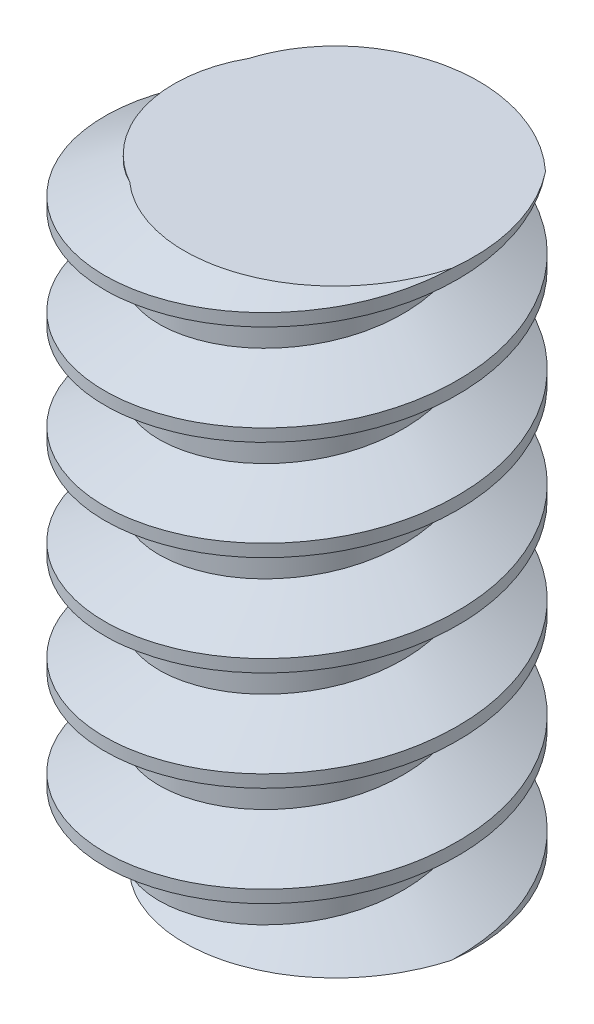
SolidWorks part; units mm, degrees
ref_plane "Front Plane" through (0, 0, 0) normal (0, 0, 1) x (1, 0, 0)
ref_plane "Top Plane" through (0, 0, 0) normal (0, 1, 0) x (1, 0, 0)
ref_plane "Right Plane" through (0, 0, 0) normal (1, 0, 0) x (0, 0, -1)
sketch "Sketch1" plane through (0, 0, 0) normal (0, 1, 0) x (1, 0, 0)
  circle A0 centre (0, 0) radius 4.5
  dimension "D1" = 9
extrude "Boss-Extrude1" add sketch "Sketch1" along normal blind 15.24
thread "Thread1" pitch 2.54 method cut profile "Thread Profile2" start angle 0, offset 3.54, length 0, pitch 2.54, diameter 9
ref_plane "Plane2" through (-4.5, 18.78, 0) normal (0, 0, 1) x (-1, 0, 0)
sketch "Thread Profile2" plane through (-4.5, 18.78, 0) normal (0, 0, 1) x (-1, 0, 0)
  line L0 (0, 0) -> (0, 2.54) construction
  line L11 (0, 0) -> (0, 2.2225)
  line L12 (0, 2.2225) -> (-1.3748, 1.4287)
  line L13 (-1.3748, 1.4287) -> (-1.3748, 0.7937)
  line L15 (-1.3748, 0.7937) -> (0, 0)
  line L17 (-1.3748, 1.1112) -> (0, 1.1112) construction
  point P2 (0, 0)
  dimension "Pitch" = 2.54
  dimension "Profile_Angle" = 60
  dimension "Profile_Land" = 0.635
  dimension "Profile_Height" = 1.3748
